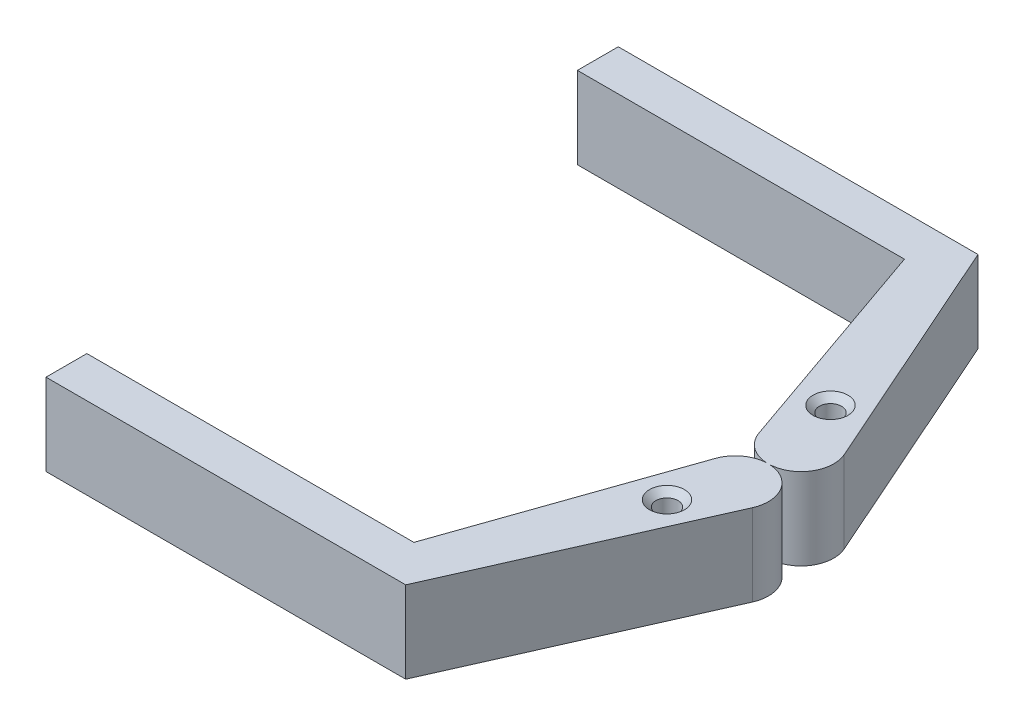
SolidWorks part; units mm, degrees
ref_plane "Front Plane" through (0, 0, 0) normal (0, 0, 1) x (1, 0, 0)
ref_plane "Top Plane" through (0, 0, 0) normal (0, 1, 0) x (1, 0, 0)
ref_plane "Right Plane" through (0, 0, 0) normal (1, 0, 0) x (0, 0, -1)
sketch "Sketch2" plane through (0, 0, 0) normal (0, 1, 0) x (1, 0, 0)
  line L0 (-12.7, 38.1) -> (-0.6089, 3.408)
  line L1 (-63.5, 44.45) -> (-12.7, 44.45)
  line L2 (-63.5, 44.45) -> (-63.5, 38.1)
  line L3 (-63.5, 38.1) -> (-12.7, 38.1)
  line L4 (-12.7, 44.45) -> (-12.7, 38.1) construction
  line L5 (-63.5, 44.45) -> (-12.7, 38.1) construction
  line L6 (-63.5, 38.1) -> (-12.7, 44.45) construction
  line L7 (-63.5, -44.45) -> (-12.7, -44.45)
  line L8 (-63.5, -44.45) -> (-63.5, -38.1)
  line L9 (-63.5, -38.1) -> (-12.7, -38.1)
  line L10 (-12.7, -44.45) -> (-12.7, -38.1) construction
  line L11 (-63.5, -44.45) -> (-12.7, -38.1) construction
  line L12 (-63.5, -38.1) -> (-12.7, -44.45) construction
  line L13 (-0.5898, -3.406) -> (-12.7, -38.1)
  line L14 (-12.7, -44.45) -> (-7.62, -44.45)
  line L15 (-7.62, -44.45) -> (8.9279, -7.1396)
  line L16 (8.9105, 7.1377) -> (-7.62, 44.45)
  line L17 (-7.62, 44.45) -> (-12.7, 44.45)
  line L18 (4.1973, -0.0001) -> (4.275, 0) construction
  arc A0 (8.9279, -7.1396) -> (4.275, 0) centre (4.2841, -5.08) ccw
  arc A1 (4.275, 0) -> (8.9105, 7.1377) centre (4.2659, 5.08) ccw
  arc A2 (4.1973, -0.0001) -> (-0.5898, -3.406) centre (4.2064, -5.0801) ccw
  arc A3 (4.1973, -0.0001) -> (-0.6089, 3.408) centre (4.1881, 5.0799) cw
  point P0 (-38.1, 41.275)
  point P5 (-38.1, -41.275)
  dimension "D13" = 5.08
  dimension "D7" = 5.08
  dimension "D8" = 5.08
  dimension "D2" = 5.08
  dimension "D3" = 6.35
  dimension "D4" = 6.35
  dimension "D5" = 5.08
  dimension "D6" = 5.08
  dimension "D10" = 50.8
  dimension "D11" = 50.8
extrude "Boss-Extrude1" add sketch "Sketch2" along normal blind 12.7
hole_wizard "#8-32 Tapped Hole1" positions "Sketch6" profile "Sketch7" tap size "#8-32" standard "ANSI Inch" end condition through all
sketch "Sketch6" plane through (0, 12.7, 0) normal (0, 1, 0) x (1, 0, 0)
  point P0 (1.2155, 12.6999)
  point P2 (1.2155, -12.7)
  dimension "D1" = 12.7
  dimension "D2" = 12.7
sketch "Sketch7" plane through (1.2155, 12.7, -12.6999) normal (1, 0, 0) x (0, 0, 1)
  line L0 (0, 0) -> (0, 12.7)
  line L1 (0, 12.7) -> (1.7272, 12.7)
  line L2 (1.7272, 12.7) -> (1.7272, 0.9906)
  line L3 (1.7272, 0.9906) -> (2.7178, 0)
  line L5 (2.7178, 0) -> (0, 0)
  line L6 (-1.7272, 0.9906) -> (-2.7178, 0) construction
  line L11 (0, -6.35) -> (0, 107.95) construction
  dimension "Thru Tap Drill Dia." = 3.4544
  dimension "Thru Tap Drill Depth" = 12.7
  dimension "Near C'Sink Dia." = 5.4356
  dimension "Near C'Sink Angle" = 90
cosmetic thread "Hole Thread1" parameters "D2"=4.1656
cosmetic thread "Hole Thread2" parameters "D2"=4.1656
sketch "Sketch8" plane through (0, 12.7, 0) normal (0, 1, 0) x (1, 0, 0)
  line L1 (-1.153, -0.7401) -> (12.9393, -0.7401)
  line L2 (-1.153, -0.7401) -> (-1.153, 0.7401)
  line L3 (-1.153, 0.7401) -> (12.9393, 0.7401)
  line L4 (12.9393, -0.7401) -> (12.9393, 0.7401)
  line L5 (-1.153, -0.7401) -> (12.9393, 0.7401) construction
  line L6 (-1.153, 0.7401) -> (12.9393, -0.7401) construction
  point P0 (5.8932, 0)
  dimension "D1" = 1.4803
